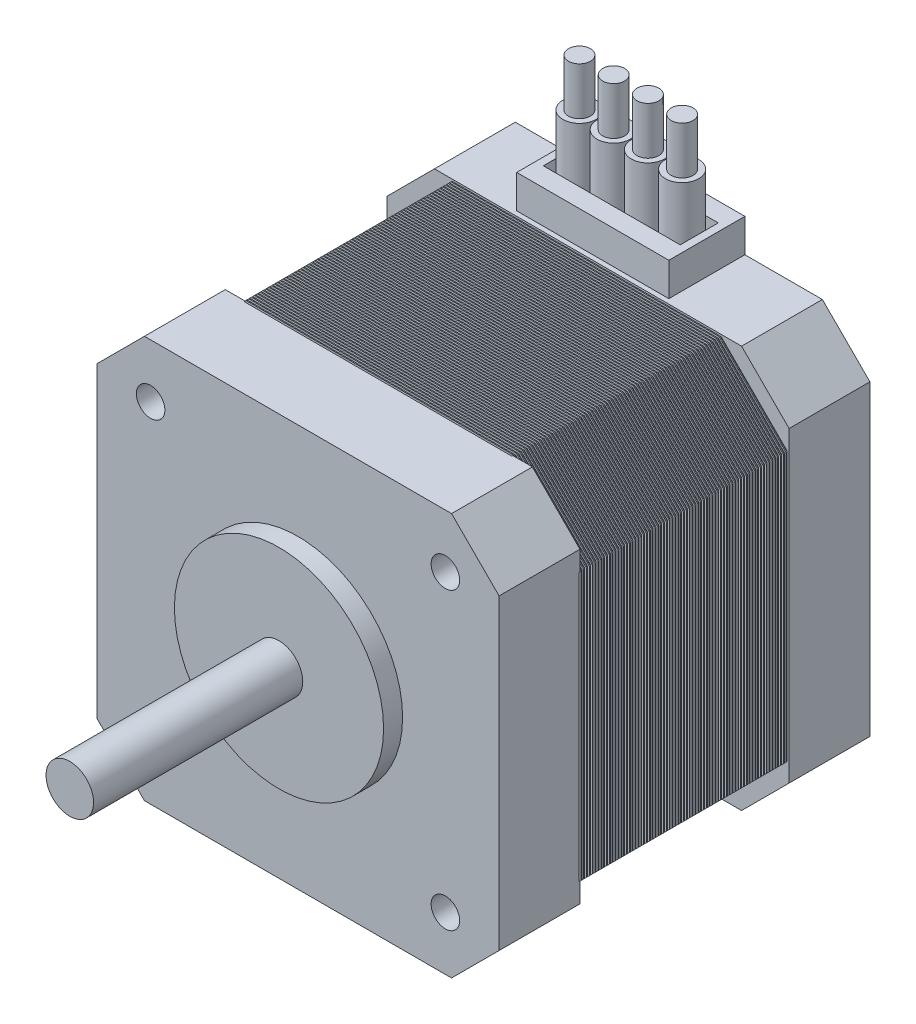
SolidWorks part; units mm, degrees
ref_plane "Front Plane" through (0, 0, 0) normal (0, 0, 1) x (1, 0, 0)
ref_plane "Top Plane" through (0, 0, 0) normal (0, 1, 0) x (1, 0, 0)
ref_plane "Right Plane" through (0, 0, 0) normal (1, 0, 0) x (0, 0, -1)
sketch "Sketch1" plane through (0, 0, 0) normal (0, 0, 1) x (1, 0, 0)
  line L0 (-21.15, 16.15) -> (-16.15, 21.15)
  line L1 (30.0787, 22.0386) -> (146.3871, 22.0386) construction
  line L2 (-16.15, -21.15) -> (16.15, -21.15)
  line L3 (-21.15, -16.15) -> (-21.15, 16.15)
  line L4 (-16.15, 21.15) -> (16.15, 21.15)
  line L5 (21.15, -16.15) -> (21.15, 16.15)
  line L6 (-21.15, -21.15) -> (21.15, 21.15) construction
  line L7 (-21.15, 21.15) -> (21.15, -21.15) construction
  line L8 (16.15, 21.15) -> (21.15, 16.15)
  line L9 (16.15, -21.15) -> (21.15, -16.15)
  line L10 (-16.15, -21.15) -> (-21.15, -16.15)
  point P0 (0, 0)
  dimension "D1" = 42.3
  dimension "D2" = 42.3
extrude "Boss-Extrude1" add sketch "Sketch1" along normal blind 39
sketch "Sketch2" plane through (0, 0, 39) normal (0, 0, 1) x (1, 0, 0)
  circle A0 centre (0, 0) radius 2.5
  dimension "D1" = 5
extrude "Boss-Extrude2" add sketch "Sketch2" along normal blind 24
sketch "Sketch3" plane through (0, 0, 39) normal (0, 0, 1) x (1, 0, 0)
  circle A0 centre (0, 0) radius 11
  dimension "D1" = 22
extrude "Boss-Extrude3" add sketch "Sketch3" along normal blind 2
sketch "Sketch4" plane through (0, 0, 39) normal (0, 0, 1) x (1, 0, 0)
  line L1 (-15.5, -15.5) -> (15.5, -15.5) construction
  line L2 (-15.5, -15.5) -> (-15.5, 15.5) construction
  line L3 (-15.5, 15.5) -> (15.5, 15.5) construction
  line L4 (15.5, -15.5) -> (15.5, 15.5) construction
  line L5 (-15.5, -15.5) -> (15.5, 15.5) construction
  line L6 (-15.5, 15.5) -> (15.5, -15.5) construction
  circle A0 centre (-15.5, 15.5) radius 1.5
  circle A1 centre (15.5, 15.5) radius 1.5
  circle A2 centre (15.5, -15.5) radius 1.5
  circle A3 centre (-15.5, -15.5) radius 1.5
  point P0 (0, 0)
  dimension "D3" = 3
  dimension "D1" = 31
  dimension "D2" = 31
extrude "Cut-Extrude1" cut sketch "Sketch4" against normal blind 4.5
sketch "Sketch5" plane through (0, 0, 0) normal (0, 0, -1) x (-1, 0, 0)
  line L0 (-21.15, 14.0789) -> (-14.0789, 21.15)
  line L5 (-21.15, 21.15) -> (21.15, -21.15) construction
  line L6 (-21.15, -21.15) -> (21.15, 21.15) construction
  line L7 (14.0789, 21.15) -> (21.15, 14.0789)
  line L8 (21.15, -14.0789) -> (14.0789, -21.15)
  line L9 (-14.0789, -21.15) -> (-21.15, -14.0789)
  line L10 (-21.15, 14.0789) -> (-21.15, 21.15)
  line L11 (-21.15, 21.15) -> (-14.0789, 21.15)
  line L12 (14.0789, 21.15) -> (21.15, 21.15)
  line L13 (21.15, 21.15) -> (21.15, 14.0789)
  line L14 (14.0789, -21.15) -> (21.15, -21.15)
  line L15 (21.15, -21.15) -> (21.15, -14.0789)
  line L16 (-21.15, -14.0789) -> (-21.15, -21.15)
  line L17 (-21.15, -21.15) -> (-14.0789, -21.15)
  point P0 (0, 0)
  point P17 (0, 0)
  dimension "D1" = 10
  dimension "D3" = 4
extrude "Cut-Extrude2" cut sketch "Sketch5" against normal blind 22 from offset 8.5 offset against normal yes
sketch "Sketch6" plane through (0, 0, 8.5) normal (0, 0, 1) x (1, 0, 0)
  line L0 (-21.15, -14.0789) -> (-14.0789, -21.15) construction
  line L1 (14.0789, -21.15) -> (21.15, -14.0789) construction
  line L2 (21.15, 14.0789) -> (14.0789, 21.15) construction
  line L3 (-14.0789, 21.15) -> (-21.15, 14.0789) construction
  line L4 (-21.15, -14.0789) -> (-14.0789, -21.15)
  line L5 (14.0789, -21.15) -> (21.15, -14.0789)
  line L6 (21.15, 14.0789) -> (14.0789, 21.15)
  line L7 (-14.0789, 21.15) -> (-21.15, 14.0789)
  line L8 (-21.15, 16.15) -> (-21.15, -16.15)
  line L9 (-16.15, 21.15) -> (-21.15, 16.15)
  line L10 (16.15, 21.15) -> (-16.15, 21.15)
  line L11 (21.15, 16.15) -> (16.15, 21.15)
  line L12 (21.15, -16.15) -> (21.15, 16.15)
  line L13 (16.15, -21.15) -> (21.15, -16.15)
  line L14 (-16.15, -21.15) -> (16.15, -21.15)
  line L15 (-21.15, -16.15) -> (-16.15, -21.15)
  line L16 (-21.15, 14.0789) -> (-21.15, -14.0789)
  line L18 (14.0789, 21.15) -> (-14.0789, 21.15)
  line L20 (21.15, -14.0789) -> (21.15, 14.0789)
  line L22 (-14.0789, -21.15) -> (14.0789, -21.15)
  line L24 (-20.95, -13.9961) -> (-13.9961, -20.95)
  line L25 (-13.9961, -20.95) -> (13.9961, -20.95)
  line L26 (13.9961, -20.95) -> (20.95, -13.9961)
  line L27 (20.95, -13.9961) -> (20.95, 13.9961)
  line L28 (20.95, 13.9961) -> (13.9961, 20.95)
  line L29 (13.9961, 20.95) -> (-13.9961, 20.95)
  line L30 (-13.9961, 20.95) -> (-20.95, 13.9961)
  line L31 (-20.95, 13.9961) -> (-20.95, -13.9961)
  dimension "D1" = 0
  dimension "D2" = 0.2
extrude "Cut-Extrude3" cut sketch "Sketch6" along normal blind 0.2
pattern_linear "LPattern1" count 74 spacing 0.3 along (0, 0, 1) of "Cut-Extrude3"
sketch "Sketch7" plane through (0, 21.15, 0) normal (0, 1, 0) x (1, 0, 0)
  line L0 (16.15, 0) -> (-16.15, 0) construction
  line L1 (-8, -8) -> (8, -8)
  line L2 (-8, -8) -> (-8, 0)
  line L3 (-8, 0) -> (8, 0)
  line L4 (8, -8) -> (8, 0)
  line L5 (-8, -8) -> (8, 0) construction
  line L6 (-8, 0) -> (8, -8) construction
  point P0 (0, -4)
  dimension "D1" = 8
  dimension "D2" = 16
extrude "Boss-Extrude4" add sketch "Sketch7" along normal blind 3.5
sketch "Sketch8" plane through (0, 24.65, 0) normal (0, 1, 0) x (1, 0, 0)
  line L4 (-7.2, -4) -> (-3.6, -4) construction
  line L5 (0, -0.8) -> (0, -7.2) construction
  line L6 (-3.6, -4) -> (-3.6, -0.8) construction
  line L7 (-3.55, -4) -> (0, -4) construction
  line L8 (7.2, -7.2) -> (7.2, -0.8)
  line L9 (7.2, -0.8) -> (-7.2, -0.8)
  line L10 (-7.2, -0.8) -> (-7.2, -7.2)
  line L11 (-7.2, -7.2) -> (7.2, -7.2)
  line L12 (7.2, -7.2) -> (7.2, -0.8)
  line L13 (7.2, -0.8) -> (-7.2, -0.8) construction
  line L14 (-7.2, -0.8) -> (-7.2, -7.2)
  line L15 (-7.2, -7.2) -> (7.2, -7.2) construction
  line L16 (-7.2, -6) -> (7.2, -6)
  line L17 (-7.2, -2) -> (7.2, -2)
  line L18 (-7.2, -2) -> (-3.6, -2) construction
  line L19 (-7.2, -6) -> (-3.6, -6) construction
  circle A0 centre (-5.4, -4) radius 1.75
  circle A1 centre (-1.8, -4) radius 1.75
  circle A2 centre (1.8, -4) radius 1.75
  circle A3 centre (5.4, -4) radius 1.75
  dimension "D2" = 1.8
  dimension "D3" = 3.5
  dimension "D4" = 3.6
  dimension "D1" = 0.8
  dimension "D5" = 2
  dimension "D6" = 2
extrude "Cut-Extrude4" cut sketch "Sketch8" against normal blind 3 contours L17 L14 L16 L12 A2 A1 A0 A3 region at (0, 24.65, 4)
sketch "Sketch9" plane through (0, 24.65, 0) normal (0, 1, 0) x (1, 0, 0)
  circle A0 centre (5.4, -4) radius 1.75 construction
  circle A3 centre (1.8, -4) radius 1.75 construction
  circle A4 centre (-5.4, -4) radius 1.75 construction
  circle A5 centre (5.4, -4) radius 1.75
  circle A6 centre (1.8, -4) radius 1.75
  circle A7 centre (-5.4, -4) radius 1.75
  circle A8 centre (-1.8, -4) radius 1.75
  circle A9 centre (-1.8, -4) radius 1.75
  dimension "D1" = 0
extrude "Boss-Extrude5" add sketch "Sketch9" along normal blind 5
sketch "Sketch10" plane through (0, 29.65, 0) normal (0, 1, 0) x (1, 0, 0)
  circle A5 centre (-5.4, -4) radius 1.15
  circle A6 centre (-5.4, -4) radius 1.15
  circle A8 centre (-1.8, -4) radius 1.15
  circle A9 centre (-1.8, -4) radius 1.15
  circle A11 centre (1.8, -4) radius 1.15
  circle A12 centre (1.8, -4) radius 1.15
  circle A14 centre (5.4, -4) radius 1.15
  circle A15 centre (5.4, -4) radius 1.15
  dimension "D1" = 0.6
  dimension "D2" = 0.6
  dimension "D3" = 0.6
  dimension "D4" = 0.6
extrude "Boss-Extrude6" add sketch "Sketch10" along normal blind 5
scale "Scale1" bodies to scale 111 scale about centroid uniform scaling yes scale factor 0.7
